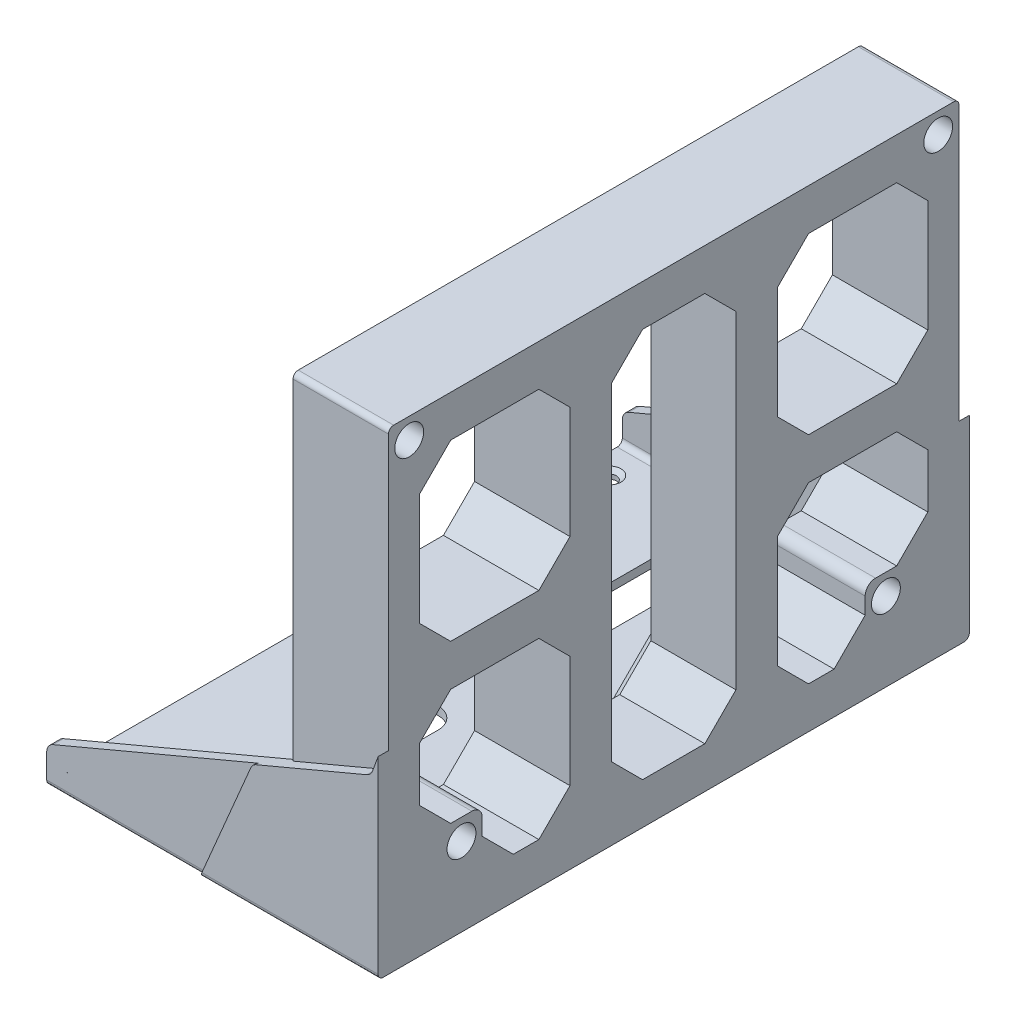
SolidWorks part; units mm, degrees
material "Nylon 101"
ref_plane "Front Plane" through (0, 0, 0) normal (0, 0, 1) x (1, 0, 0)
ref_plane "Top Plane" through (0, 0, 0) normal (0, 1, 0) x (1, 0, 0)
ref_plane "Right Plane" through (0, 0, 0) normal (1, 0, 0) x (0, 0, -1)
sketch "Sketch2" plane through (149.225, 0, 0) normal (1, 0, 0) x (0, 0, -1)
  line L8 (-6.477, 0) -> (-6.477, -144.78)
  line L9 (-6.477, -144.78) -> (174.498, -144.78)
  line L10 (174.498, -144.78) -> (174.498, 0)
  line L11 (174.498, 0) -> (-6.477, 0)
extrude "Boss-Extrude1" add sketch "Sketch2" against normal up to surface (149.225 mm away)
sketch "Sketch3" plane through (0, 0, 6.477) normal (0, 0, 1) x (1, 0, 0)
  line L0 (60.325, 0) -> (0, 0)
  line L1 (0, 0) -> (0, -102.8733)
  line L2 (0, -144.78) -> (0, 0) construction
  line L12 (-9.2712, -106.7829) -> (-25.4, -144.78)
  line L13 (-25.4, -144.78) -> (149.225, -144.78)
  line L14 (149.225, -144.78) -> (149.225, 0)
  line L15 (149.225, 0) -> (60.325, 0)
  line L16 (60.325, 0) -> (27.031, -91.4744)
  line L17 (27.031, -91.4744) -> (-9.2712, -106.7829)
extrude "Boss-Extrude2" add sketch "Sketch3<3>" against normal blind 3.175 contours L16 L17 L12 L13 L14 L15
sketch "Sketch3<3>" plane through (0, 0, 6.477) normal (0, 0, 1) x (1, 0, 0) same geometry as "Sketch3"
sketch "Sketch4" plane through (0, 0, 0.127) normal (0, 0, 1) x (1, 0, 0)
  line L8 (-73.025, -133.6675) -> (-73.025, -144.78)
  line L9 (-73.025, -144.78) -> (-25.4, -144.78)
  line L10 (-25.4, -144.78) -> (-9.2712, -106.7829)
  line L11 (-9.2712, -106.7829) -> (-73.025, -133.6675)
extrude "Boss-Extrude3" add sketch "Sketch4" along normal blind 3.175
sketch "Sketch5" plane through (0, 0, 3.302) normal (0, 0, -1) x (-1, 0, 0)
  line L4 (0, -102.8733) -> (0, -144.78)
  line L5 (0, -144.78) -> (25.4, -144.78)
  line L6 (25.4, -144.78) -> (9.2712, -106.7829)
  line L7 (9.2712, -106.7829) -> (0, -102.8733)
  line L8 (0, -102.8733) -> (0, -144.78)
  line L9 (0, -144.78) -> (25.4, -144.78)
  line L10 (25.4, -144.78) -> (9.2712, -106.7829)
  line L11 (9.2712, -106.7829) -> (0, -102.8733)
  dimension "D1" = 0
extrude "Boss-Extrude4" add sketch "Sketch5" along normal blind 3.175
ref_plane "Plane1" through (0, 0, -84.0105) normal (0, 0, 1) x (1, 0, 0)
mirror "Mirror5" about plane through (0, 0, -84.0105) normal (0, 0, 1) of bodies 105 104
extrude "Cut-Extrude1" cut sketch "Sketch3" against normal blind 3.175 contours L0 L1 region at (22.3809, -41.9815, 6.477)
mirror "Mirror6" about plane through (0, 0, -84.0105) normal (0, 0, 1) of "Cut-Extrude1"
sketch "Sketch7" plane through (0, -144.78, 0) normal (0, -1, 0) x (1, 0, 0)
  line L1 (0, 0.127) -> (-73.025, 0.127)
  line L2 (0, 0.127) -> (0, -171.323)
  line L3 (0, -171.323) -> (-73.025, -171.323)
  line L4 (-73.025, 0.127) -> (-73.025, -171.323)
  line L5 (0, 0.127) -> (-73.025, -171.323) construction
  line L6 (0, -171.323) -> (-73.025, 0.127) construction
  line L8 (-73.025, 3.302) -> (-73.025, 0.127) construction
  line L10 (0, -168.148) -> (0, 0.127) construction
  point P4 (-36.5125, -85.598)
extrude "Boss-Extrude6" add sketch "Sketch7" against normal blind 2.54
fillet "Fillet1" radius 1.5875 2 edges at (30.1625, 0, -171.323) (30.1625, 0, 3.302)
sketch "Sketch10" plane through (149.225, 0, 0) normal (1, 0, 0) x (0, 0, -1)
  line L8 (161.798, -12.7) -> (6.223, -12.7)
  line L9 (6.223, -12.7) -> (6.223, -132.08)
  line L10 (6.223, -132.08) -> (161.798, -132.08)
  line L11 (161.798, -132.08) -> (161.798, -12.7)
  line L12 (161.798, -12.7) -> (6.223, -12.7)
  line L13 (6.223, -12.7) -> (6.223, -132.08)
  line L14 (6.223, -132.08) -> (161.798, -132.08)
  line L15 (161.798, -132.08) -> (161.798, -12.7)
  dimension "D1" = 12.7
extrude "Cut-Extrude2" cut sketch "Sketch10" against normal through all
fillet "Fillet3" radius 3.175 6 edges at (-73.025, -133.6675, -169.7355) (-9.2712, -106.7829, -172.9105) (27.031, -91.4744, -172.9105) (-9.2712, -106.7829, 4.8895) (-73.025, -133.6675, 1.7145) (27.031, -91.4744, 4.8895)
chamfer "Chamfer1" distance 6.35 angle 45 4 edges at (74.6125, -12.7, -6.223) (74.6125, -132.08, -6.223) (74.6125, -132.08, -161.798) (74.6125, -12.7, -161.798)
fillet "Fillet4" radius 6.35 8 edges at (74.6125, -132.08, -155.448) (74.6125, -132.08, -12.573) (74.6125, -125.73, -6.223) (74.6125, -19.05, -6.223) (74.6125, -12.7, -12.573) (74.6125, -12.7, -155.448) (74.6125, -19.05, -161.798) (74.6125, -125.73, -161.798)
sketch "Sketch11" plane through (149.225, 0, 0) normal (1, 0, 0) x (0, 0, -1)
  line L4 (174.498, 0) -> (-6.477, 0)
  line L5 (-6.477, 0) -> (-6.477, -144.78)
  line L6 (-6.477, -144.78) -> (174.498, -144.78)
  line L7 (174.498, -144.78) -> (174.498, 0)
  line L8 (174.498, 0) -> (-6.477, 0)
  line L9 (-6.477, 0) -> (-6.477, -144.78)
  line L10 (-6.477, -144.78) -> (174.498, -144.78)
  line L11 (174.498, -144.78) -> (174.498, 0)
  dimension "D1" = 0
extrude "Cut-Extrude3" cut sketch "Sketch11" against normal blind 82.55
fillet "Fillet5" [suppressed] radius 1.5875 tangent propagation no
sketch "Sketch12" plane through (0, -144.78, 0) normal (0, -1, 0) x (1, 0, 0)
  line L2 (-38.1, -101.473) -> (-38.1, -152.273)
  line L3 (-38.1, -101.473) -> (-38.1, -152.273)
  line L4 (-25.4, -152.273) -> (-25.4, -101.473)
  line L5 (-25.4, -152.273) -> (-25.4, -101.473)
  line L37 (-25.4, -66.548) -> (-25.4, -15.748)
  line L38 (-38.1, -15.748) -> (-38.1, -66.548)
  line L39 (-25.4, -66.548) -> (-25.4, -15.748)
  line L40 (-38.1, -15.748) -> (-38.1, -66.548)
  arc A3 (-38.1, -152.273) -> (-25.4, -152.273) centre (-31.75, -152.273) ccw
  arc A4 (-38.1, -152.273) -> (-25.4, -152.273) centre (-31.75, -152.273) ccw
  arc A5 (-25.4, -101.473) -> (-38.1, -101.473) centre (-31.75, -101.473) ccw
  arc A6 (-25.4, -101.473) -> (-38.1, -101.473) centre (-31.75, -101.473) ccw
  arc A34 (-25.4, -15.748) -> (-38.1, -15.748) centre (-31.75, -15.748) ccw
  arc A35 (-38.1, -66.548) -> (-25.4, -66.548) centre (-31.75, -66.548) ccw
  arc A36 (-25.4, -15.748) -> (-38.1, -15.748) centre (-31.75, -15.748) ccw
  arc A37 (-38.1, -66.548) -> (-25.4, -66.548) centre (-31.75, -66.548) ccw
  dimension "D1" = 0
  dimension "D2" = 0
extrude "Cut-Extrude4" cut sketch "Sketch12" against normal up to next
sketch "Sketch18" plane through (66.675, 0, 0) normal (1, 0, 0) x (0, 0, -1)
  line L0 (162.7855, -114.3) -> (145.796, -114.3) construction
  line L1 (142.621, -117.475) -> (142.621, -130.175) construction
  line L2 (152.8177, -132.08) -> (15.2033, -132.08) construction
  line L3 (159.9381, -127.5899) -> (157.3079, -130.2201) construction
  line L4 (161.798, -21.6803) -> (161.798, -123.0997) construction
  line L5 (161.798, -114.3) -> (145.796, -114.3)
  line L6 (142.621, -117.475) -> (142.621, -132.08)
  line L7 (152.8177, -132.08) -> (142.621, -132.08)
  line L8 (159.9381, -127.5899) -> (157.3079, -130.2201)
  line L9 (161.798, -114.3) -> (161.798, -123.0997)
  line L10 (84.0105, -132.08) -> (84.0105, -72.39) construction
  line L11 (84.0105, -72.39) -> (6.223, -72.39) construction
  line L12 (6.223, -123.0997) -> (6.223, -21.6803) construction
  line L13 (6.223, -114.3) -> (6.223, -123.0997)
  line L14 (8.0829, -127.5899) -> (10.7131, -130.2201)
  line L15 (15.2033, -132.08) -> (25.4, -132.08)
  line L16 (25.4, -117.475) -> (25.4, -132.08)
  line L17 (6.223, -114.3) -> (22.225, -114.3)
  line L18 (6.223, -30.48) -> (22.225, -30.48)
  line L19 (25.4, -27.305) -> (25.4, -12.7)
  line L20 (15.2033, -12.7) -> (25.4, -12.7)
  line L21 (8.0829, -17.1901) -> (10.7131, -14.5599)
  line L22 (6.223, -30.48) -> (6.223, -21.6803)
  line L23 (161.798, -30.48) -> (161.798, -21.6803)
  line L24 (159.9381, -17.1901) -> (157.3079, -14.5599)
  line L25 (152.8177, -12.7) -> (142.621, -12.7)
  line L26 (142.621, -27.305) -> (142.621, -12.7)
  line L27 (161.798, -30.48) -> (145.796, -30.48)
  arc A0 (145.796, -114.3) -> (142.621, -117.475) centre (145.796, -117.475) ccw construction
  arc A1 (152.8177, -132.08) -> (157.3079, -130.2201) centre (152.8177, -125.73) ccw construction
  arc A2 (159.9381, -127.5899) -> (161.798, -123.0997) centre (155.448, -123.0997) ccw construction
  arc A3 (145.796, -114.3) -> (142.621, -117.475) centre (145.796, -117.475) ccw
  arc A4 (152.8177, -132.08) -> (157.3079, -130.2201) centre (152.8177, -125.73) ccw
  arc A5 (159.9381, -127.5899) -> (161.798, -123.0997) centre (155.448, -123.0997) ccw
  arc A6 (8.0829, -127.5899) -> (6.223, -123.0997) centre (12.573, -123.0997) cw
  arc A7 (15.2033, -132.08) -> (10.7131, -130.2201) centre (15.2033, -125.73) cw
  arc A8 (22.225, -114.3) -> (25.4, -117.475) centre (22.225, -117.475) cw
  arc A9 (22.225, -30.48) -> (25.4, -27.305) centre (22.225, -27.305) ccw
  arc A10 (15.2033, -12.7) -> (10.7131, -14.5599) centre (15.2033, -19.05) ccw
  arc A11 (8.0829, -17.1901) -> (6.223, -21.6803) centre (12.573, -21.6803) ccw
  arc A12 (159.9381, -17.1901) -> (161.798, -21.6803) centre (155.448, -21.6803) cw
  arc A13 (152.8177, -12.7) -> (157.3079, -14.5599) centre (152.8177, -19.05) cw
  arc A14 (145.796, -30.48) -> (142.621, -27.305) centre (145.796, -27.305) cw
  line M12 (15.2033, -12.7) -> (152.8177, -12.7)
  arc M13 (152.8177, -12.7) -> (157.3079, -14.5599) centre (152.8177, -19.05) cw
  line M14 (157.3079, -14.5599) -> (159.9381, -17.1901)
  arc M15 (159.9381, -17.1901) -> (161.798, -21.6803) centre (155.448, -21.6803) cw
  line M16 (161.798, -21.6803) -> (161.798, -123.0997)
  arc M17 (161.798, -123.0997) -> (159.9381, -127.5899) centre (155.448, -123.0997) cw
  line M18 (159.9381, -127.5899) -> (157.3079, -130.2201)
  arc M19 (157.3079, -130.2201) -> (152.8177, -132.08) centre (152.8177, -125.73) cw
  line M20 (152.8177, -132.08) -> (15.2033, -132.08)
  arc M21 (15.2033, -132.08) -> (10.7131, -130.2201) centre (15.2033, -125.73) cw
  line M22 (10.7131, -130.2201) -> (8.0829, -127.5899)
  arc M23 (8.0829, -127.5899) -> (6.223, -123.0997) centre (12.573, -123.0997) cw
  line M24 (6.223, -123.0997) -> (6.223, -21.6803)
extrude "Boss-Extrude7" add sketch "Sketch18" against normal up to surface (66.675 mm away) contours A8 L17 L16 M24 M23 M22 M21 M20 | L5 A3 L6 M20 M19 M18 M17 M16 region at (66.675, -122.7851, -151.7611) region at (66.675, -122.7851, -16.2599) up to face at (0, -72.39, -84.0105)
extrude "Boss-Extrude8" add sketch "Sketch18<3>" against normal blind 9.525 contours A14 L27 L26 M16 M15 M14 M13 M12 | L19 L20 A10 L21 A11 L22 L18 A9 region at (66.675, -21.9949, -151.7611)
sketch "Sketch18<3>" plane through (66.675, 0, 0) normal (1, 0, 0) x (0, 0, -1) same geometry as "Sketch18"
hole_wizard "S (0.348) Diameter Hole1" positions "Sketch9" profile "Sketch8" hole size "S" standard "ANSI Inch" end condition through all
sketch "Sketch9" plane through (0, 0, 0) normal (-1, 0, 0) x (0, 0, 1)
  point P0 (-164.973, -6.35)
  point P3 (-3.048, -6.35)
  point P6 (-19.05, -120.65)
  point P9 (-148.971, -120.65)
sketch "Sketch8" plane through (0, -6.35, -164.973) normal (0, 1, 0) x (0, 0, 1)
  line L0 (0, 0) -> (0, 66.675)
  line L1 (0, 66.675) -> (4.4196, 66.675)
  line L2 (4.4196, 66.675) -> (4.4196, 0)
  line L5 (4.4196, 0) -> (0, 0)
  line L11 (0, -6.35) -> (0, 107.95) construction
  dimension "Thru Hole Dia." = 8.8392
  dimension "Thru Hole Depth" = 66.675
hole_wizard "CSK for #6 Flat Head Machine Screw (100)1" positions "Sketch16" profile "Sketch17" countersink size "#6" standard "ANSI Inch" end condition through all
sketch "Sketch16" plane through (0, -142.24, 0) normal (0, 1, 0) x (1, 0, 0)
  line L0 (-73.025, -3.302) -> (-73.025, 171.323) construction
  line L1 (-11.1125, 51.0043) -> (-11.1125, 2.7167) construction
  line L2 (-18.7187, -4.8895) -> (-40.6538, -4.8895) construction
  line L3 (-6.35, 84.0105) -> (-139.7, 84.0105) construction
  line L4 (-6.35, -8.8582) -> (-6.35, 176.8792) construction
  line L7 (-20.6375, 160.2105) -> (-66.675, 7.8105) construction
  point P0 (-20.6375, 7.8105)
  point P2 (-66.675, 7.8105)
  point P20 (-66.675, 160.2105)
  point P21 (-20.6375, 160.2105)
  point P26 (-43.6562, 84.0105)
  dimension "D1" = 6.35
  dimension "D2" = 9.525
  dimension "D3" = 12.7
sketch "Sketch17" plane through (-20.6375, -142.24, -7.8105) normal (1, 0, 0) x (0, 0, 1)
  line L0 (0, 0) -> (0, 2.54)
  line L1 (0, 2.54) -> (2.1526, 2.54)
  line L2 (2.1526, 2.54) -> (2.1526, 1.1669)
  line L3 (2.1526, 1.1669) -> (3.5433, 0)
  line L5 (3.5433, 0) -> (0, 0)
  line L6 (-2.1526, 1.1669) -> (-3.5433, 0) construction
  line L11 (0, -6.35) -> (0, 107.95) construction
  dimension "Thru Hole Dia." = 4.3053
  dimension "Thru Hole Depth" = 2.54
  dimension "Near C'Sink Dia." = 7.0866
  dimension "Near C'Sink Angle" = 100
hole_wizard "1/4 Clearance Hole1" positions "Sketch20" profile "Sketch21" hole size "1/4" standard "ANSI Inch" end condition through all
sketch "Sketch20" plane through (57.15, 0, 0) normal (-1, 0, 0) x (0, 0, 1)
  line L0 (-6.223, -30.48) -> (-22.225, -30.48) construction
  line L1 (-25.4, -27.305) -> (-25.4, -12.7) construction
  line L2 (-84.0105, -12.7) -> (-84.0105, -132.08) construction
  line L3 (-25.4, -12.7) -> (-142.621, -12.7) construction
  line L4 (-142.621, -132.08) -> (-25.4, -132.08) construction
  point P0 (-19.05, -24.13)
  point P16 (-148.971, -24.13)
  dimension "D1" = 6.35
  dimension "D2" = 6.35
sketch "Sketch21" plane through (57.15, -24.13, -19.05) normal (0, 1, 0) x (0, 0, 1)
  line L0 (0, 0) -> (0, 9.525)
  line L1 (0, 9.525) -> (3.5712, 9.525)
  line L2 (3.5712, 9.525) -> (3.5712, 0)
  line L5 (3.5712, 0) -> (0, 0)
  line L11 (0, -6.35) -> (0, 107.95) construction
  dimension "Thru Hole Dia." = 7.1425
  dimension "Thru Hole Depth" = 9.525
sketch "Sketch22" plane through (66.675, 0, 0) normal (1, 0, 0) x (0, 0, -1)
  line L4 (-6.477, -144.78) -> (174.498, -144.78)
  line L5 (174.498, -144.78) -> (174.498, 0)
  line L6 (174.498, 0) -> (-6.477, 0)
  line L7 (-6.477, 0) -> (-6.477, -144.78)
  line L8 (-6.477, -144.78) -> (174.498, -144.78)
  line L9 (174.498, -144.78) -> (174.498, 0)
  line L10 (174.498, 0) -> (-6.477, 0)
  line L11 (-6.477, 0) -> (-6.477, -144.78)
  dimension "D1" = 0
extrude "Relief for MIP face support" cut sketch "Sketch22" against normal offset from surface (37.465 mm away) 102.235 up to face at (-73.025, -139.6422, -84.0105)
sketch "Sketch23" plane through (29.21, 0, 0) normal (1, 0, 0) x (0, 0, -1)
  line L0 (84.0105, -132.08) -> (84.0105, -12.7)
  line L1 (142.621, -132.08) -> (25.4, -132.08) construction
  line L2 (15.2033, -12.7) -> (152.8177, -12.7) construction
  line L3 (161.798, -67.9901) -> (6.223, -67.9901)
  line L4 (161.798, -21.6803) -> (161.798, -114.3) construction
  line L5 (6.223, -114.3) -> (6.223, -21.6803) construction
extrude "Extrude-Thin1" add sketch "Sketch23" against normal up to surface (29.21 mm away) thin up to face at (0, -6.35, -160.5534) thin type mid plane wall 6.35
fillet "Fillet6" radius 6.35 12 edges at (14.605, -12.7, -80.8355) (14.605, -12.7, -87.1855) (14.605, -64.8151, -161.798) (14.605, -71.1651, -161.798) (14.605, -132.08, -87.1855) (14.605, -132.08, -80.8355) (14.605, -71.1651, -80.8355) (14.605, -71.1651, -87.1855) (14.605, -64.8151, -6.223) (14.605, -71.1651, -6.223) (14.605, -64.8151, -80.8355) (14.605, -64.8151, -87.1855)
sketch "Sketch24" plane through (29.21, 0, 0) normal (1, 0, 0) x (0, 0, -1)
  line L0 (22.225, -114.3) -> (6.223, -114.3) construction
  line L1 (25.4, -132.08) -> (25.4, -114.3)
  line L2 (25.4, -114.3) -> (6.223, -114.3)
  line L3 (6.223, -114.3) -> (6.223, -12.7)
  line L4 (6.223, -12.7) -> (161.798, -12.7)
  line L5 (15.2033, -12.7) -> (74.4855, -12.7) construction
  line L6 (84.0105, 0) -> (84.0105, -144.78) construction
  line L7 (-1.7145, 0) -> (169.7355, 0) construction
  line L8 (174.498, -144.78) -> (-6.477, -144.78) construction
  line L9 (25.4, -132.08) -> (142.621, -132.08)
  line L10 (161.798, -114.3) -> (161.798, -12.7)
  line L11 (142.621, -114.3) -> (161.798, -114.3)
  line L12 (142.621, -132.08) -> (142.621, -114.3)
  point P19 (84.0105, -132.08)
  point P21 (84.0105, -12.7)
extrude "Cut-Extrude5" cut sketch "Sketch24" against normal up to surface (29.21 mm away) up to face at (0, -34.5124, -37.0344)
sketch "Sketch25" plane through (29.21, 0, 0) normal (1, 0, 0) x (0, 0, -1)
  line L0 (84.0105, -132.08) -> (84.0105, -12.7) construction
  line L1 (142.621, -132.08) -> (25.4, -132.08) construction
  line L2 (6.223, -12.7) -> (161.798, -12.7) construction
  line L3 (58.6105, -132.08) -> (58.6105, -12.7)
  line L4 (58.6105, -72.39) -> (6.223, -72.39)
  line L5 (6.223, -114.3) -> (6.223, -12.7) construction
  line L6 (109.4105, -72.39) -> (161.798, -72.39)
  line L7 (109.4105, -132.08) -> (109.4105, -12.7)
  dimension "D1" = 25.4
extrude "Extrude-Thin2" add sketch "Sketch25" against normal up to surface (29.21 mm away) thin up to face at (0, -98.0395, -84.0105) thin type mid plane wall 12.7
chamfer "Chamfer2" distance 9.525 angle 45 22 edges at (14.605, -132.08, -25.4) (14.605, -114.3, -6.223) (14.605, -78.74, -6.223) (14.605, -78.74, -52.2605) (14.605, -132.08, -52.2605) (14.605, -66.04, -52.2605) (14.605, -66.04, -6.223) (14.605, -12.7, -6.223) (14.605, -12.7, -52.2605) (14.605, -12.7, -103.0605) (14.605, -12.7, -64.9605) (14.605, -132.08, -64.9605) (14.605, -132.08, -103.0605) (14.605, -132.08, -115.7605) (14.605, -132.08, -142.621) (14.605, -114.3, -161.798) (14.605, -78.74, -161.798) (14.605, -78.74, -115.7605) (14.605, -66.04, -115.7605) (14.605, -66.04, -161.798) (14.605, -12.7, -161.798) (14.605, -12.7, -115.7605)
chamfer "Chamfer3" distance 3.175 angle 45 8 edges at (0, -127.3175, -69.723) (0, -72.39, -64.9605) (0, -17.4625, -69.723) (0, -12.7, -84.0105) (0, -17.4625, -98.298) (0, -72.39, -103.0605) (0, -127.3175, -98.298) (0, -132.08, -84.0105)
sketch "Sketch26" plane through (0, 0, 3.302) normal (0, 0, 1) x (1, 0, 0)
  line L4 (-8.0852, -106.2827) -> (-71.0837, -132.8489)
  line L5 (-73.025, -135.7744) -> (-73.025, -144.78)
  line L6 (-73.025, -144.78) -> (-25.4, -144.78)
  line L7 (-25.4, -144.78) -> (-9.7741, -107.9677)
  line L8 (-8.0852, -106.2827) -> (-71.0837, -132.8489)
  line L9 (-73.025, -135.7744) -> (-73.025, -144.78)
  line L10 (-73.025, -144.78) -> (-25.4, -144.78)
  line L11 (-25.4, -144.78) -> (-9.7741, -107.9677)
  arc A2 (-71.0837, -132.8489) -> (-73.025, -135.7744) centre (-69.85, -135.7744) ccw
  arc A3 (-8.0852, -106.2827) -> (-9.7741, -107.9677) centre (-6.8515, -109.2083) ccw
  arc A4 (-71.0837, -132.8489) -> (-73.025, -135.7744) centre (-69.85, -135.7744) ccw
  arc A5 (-8.0852, -106.2827) -> (-9.7741, -107.9677) centre (-6.8515, -109.2083) ccw
  dimension "D1" = 0
extrude "Boss-Extrude9" add sketch "Sketch26" along normal blind 2.3813
sketch "Sketch28" plane through (0, 0, 0.127) normal (0, 0, -1) x (-1, 0, 0)
  line L4 (73.025, -142.24) -> (73.025, -135.7744)
  line L5 (71.0837, -132.8489) -> (0, -102.8733)
  line L6 (0, -102.8733) -> (0, -142.24)
  line L7 (0, -142.24) -> (73.025, -142.24)
  line L8 (73.025, -142.24) -> (73.025, -135.7744)
  line L9 (71.0837, -132.8489) -> (0, -102.8733)
  line L10 (0, -102.8733) -> (0, -142.24)
  line L11 (0, -142.24) -> (73.025, -142.24)
  arc A1 (73.025, -135.7744) -> (71.0837, -132.8489) centre (69.85, -135.7744) ccw
  arc A2 (73.025, -135.7744) -> (71.0837, -132.8489) centre (69.85, -135.7744) ccw
  dimension "D1" = 0
extrude "Cut-Extrude6" cut sketch "Sketch28" against normal blind 2.3813
mirror "Mirror10" about plane through (0, 0, -84.0105) normal (0, 0, 1) of "Cut-Extrude6", "Boss-Extrude9"
fillet "Fillet7" radius 1.5875 4 edges at (-36.5125, -142.24, 2.5082) (-49.2125, -144.78, 5.6832) (-49.2125, -144.78, -173.7043) (-36.5125, -142.24, -170.5293)
fillet "Fillet8" radius 1.5875 2 edges at (1.905, -144.78, 6.477) (1.905, -144.78, -174.498)
